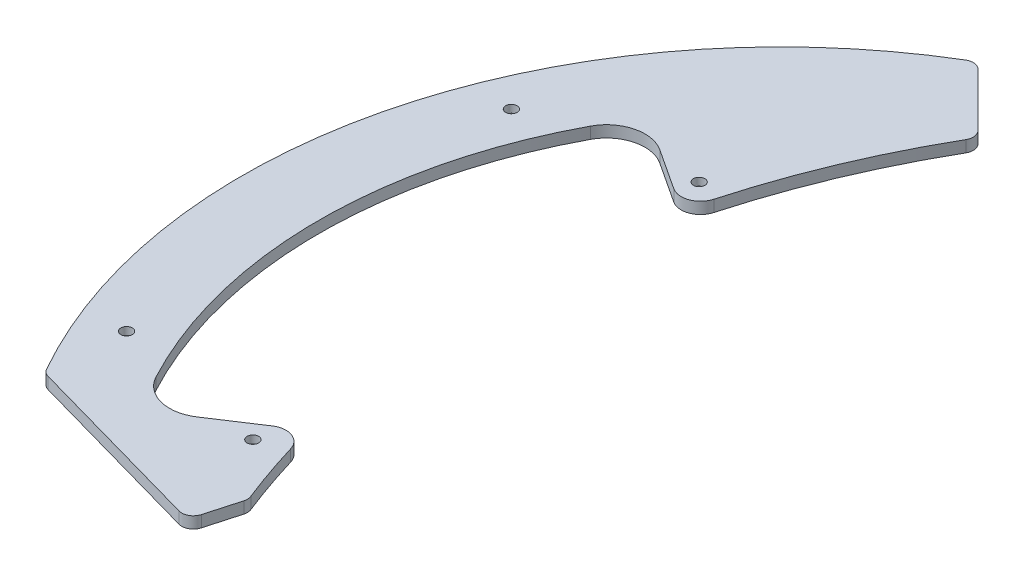
SolidWorks part; units mm, degrees
material "1060 Alloy"
ref_plane "Front Plane" through (0, 0, 0) normal (0, 0, 1) x (1, 0, 0)
ref_plane "Top Plane" through (0, 0, 0) normal (0, 1, 0) x (1, 0, 0)
ref_plane "Right Plane" through (0, 0, 0) normal (1, 0, 0) x (0, 0, -1)
sketch "Sketch1" plane through (0, 0, 0) normal (0, 1, 0) x (1, 0, 0)
  circle A0 centre (0, 0) radius 140
  dimension "D1" = 280
extrude "Boss-Extrude1" add sketch "Sketch1" along normal blind 3
sketch "Sketch17" plane through (0, 0, 0) normal (0, -1, 0) x (1, 0, 0)
  line L0 (-50, 90) -> (-121.2436, 70)
  line L1 (-50, 90) -> (50, 90)
  line L2 (-121.2436, 70) -> (-121.2436, 140)
  line L3 (-121.2436, 140) -> (121.2436, 140)
  line L4 (121.2436, 140) -> (121.2436, 70)
  line L5 (121.2436, 70) -> (50, 90)
  circle A0 centre (0, 0) radius 140 construction
  dimension "D1" = 90
  dimension "D2" = 50
  dimension "D3" = 50
  dimension "D4" = 70
extrude "Cut-Extrude1" cut sketch "Sketch17" against normal up to next
sketch "Sketch19" plane through (0, 3, 0) normal (0, 1, 0) x (1, 0, 0)
  line L0 (-68.5894, 68.5894) -> (68.5894, -68.5894) construction
  line L1 (97, 40.1787) -> (40.1787, 97) construction
  line L2 (40.1787, 97) -> (-40.1787, 97) construction
  line L3 (-40.1787, 97) -> (-97, 40.1787) construction
  line L4 (-97, 40.1787) -> (-97, -40.1787) construction
  line L5 (-97, -40.1787) -> (-40.1787, -97) construction
  line L6 (-40.1787, -97) -> (40.1787, -97) construction
  line L7 (40.1787, -97) -> (97, -40.1787) construction
  line L8 (97, -40.1787) -> (97, 40.1787) construction
  line L9 (68.5894, 68.5894) -> (-68.5894, -68.5894) construction
  circle A0 centre (-79.196, -57.9828) radius 1.5
  circle A1 centre (-79.196, 57.9828) radius 1.5
  circle A2 centre (79.196, 57.9828) radius 1.5
  circle A3 centre (79.196, -57.9828) radius 1.5
  circle A4 centre (0, 0) radius 97 construction
  circle A5 centre (-57.9828, 79.196) radius 1.5
  circle A6 centre (57.9828, 79.196) radius 1.5
  circle A7 centre (57.9828, -79.196) radius 1.5
  circle A8 centre (-57.9828, -79.196) radius 1.5
  dimension "D5" = 3
  dimension "D1" = 15
  dimension "D6" = 97
extrude "Cut-Extrude3" cut sketch "Sketch19" against normal up to next
sketch "Sketch20" plane through (0, 3, 0) normal (0, 1, 0) x (1, 0, 0)
  line L0 (-70, 121.2436) -> (-50, 101.2436)
  line L1 (-50, 101.2436) -> (50, 101.2436)
  line L2 (50, 101.2436) -> (70, 121.2436)
  arc A1 (121.2436, -70) -> (-121.2436, -70) centre (0, 0) ccw construction
  dimension "D1" = 140
  dimension "D2" = 100
  dimension "D3" = 50
extrude "Cut-Extrude4" cut sketch "Sketch20" against normal up to next
sketch "Sketch21" plane through (0, 3, 0) normal (0, 1, 0) x (1, 0, 0)
  line L0 (-52.1633, 87.3282) -> (0, 50)
  line L1 (0, 50) -> (52.1633, 87.3282)
  line L2 (66.2648, 73.5916) -> (30, 20)
  line L3 (30, 20) -> (67.2983, -75.56)
  line L4 (49.6537, -84.7301) -> (0, -10) construction
  line L5 (0, -10) -> (-49.6537, -84.7301) construction
  line L6 (-67.2983, -75.56) -> (-30, 20)
  line L7 (-30, 20) -> (-66.2648, 73.5916)
  line L8 (-67.2983, -75.56) -> (-72.9344, -90)
  line L9 (-72.9344, -90) -> (72.9344, -90)
  line L10 (72.9344, -90) -> (67.2983, -75.56)
  line L11 (-50, -90) -> (50, -90) construction
  line L12 (-68.5894, 68.5894) -> (68.5894, -68.5894) construction
  line L13 (97, 40.1787) -> (40.1787, 97) construction
  line L14 (40.1787, 97) -> (-40.1787, 97) construction
  line L15 (-40.1787, 97) -> (-97, 40.1787) construction
  line L16 (-97, 40.1787) -> (-97, -40.1787) construction
  line L17 (-97, -40.1787) -> (-40.1787, -97) construction
  line L18 (-40.1787, -97) -> (40.1787, -97) construction
  line L19 (40.1787, -97) -> (97, -40.1787) construction
  line L20 (97, -40.1787) -> (97, 40.1787) construction
  line L21 (68.5894, 68.5894) -> (-68.5894, -68.5894) construction
  arc A0 (-66.2648, 73.5916) -> (-52.1633, 87.3282) centre (-57.9828, 79.196) cw
  arc A1 (66.2648, 73.5916) -> (52.1633, 87.3282) centre (57.9828, 79.196) ccw
  arc A2 (-49.6537, -84.7301) -> (-67.2983, -75.56) centre (-57.9828, -79.196) cw construction
  arc A3 (67.2983, -75.56) -> (49.6537, -84.7301) centre (57.9828, -79.196) cw construction
  circle A5 centre (0, 0) radius 97 construction
  dimension "D2" = 10
  dimension "D3" = 15
  dimension "D8" = 97
extrude "Cut-Extrude5" [suppressed] cut sketch "Sketch21" against normal up to next
fillet "Fillet1" [suppressed] radius 20
fillet "Fillet2" radius 10 2 edges at (50, 1.5, -101.2436) (-50, 1.5, -101.2436)
sketch "Sketch22" plane through (0, 3, 0) normal (0, 1, 0) x (1, 0, 0)
  line L1 (85, 24) -> (118, 24)
  line L2 (85, 24) -> (85, -24)
  line L3 (85, -24) -> (118, -24)
  line L4 (118, 24) -> (118, -24)
  line L5 (-118, 26) -> (-85, 26)
  line L6 (-118, 26) -> (-118, -27)
  line L7 (-118, -27) -> (-85, -27)
  line L8 (-85, 26) -> (-85, -27)
  dimension "D1" = 85
  dimension "D2" = 85
  dimension "D3" = 48
  dimension "D4" = 53
  dimension "D5" = 33
  dimension "D6" = 33
  dimension "D7" = 26
  dimension "D8" = 24
extrude "Cut-Extrude6" [suppressed] cut sketch "Sketch22" against normal up to next
fillet "Fillet3" [suppressed] radius 3
sketch "Sketch23" plane through (0, 3, 0) normal (0, 1, 0) x (1, 0, 0)
  line L0 (-66.3365, -71.9548) -> (-73.1897, -96.3671)
  line L1 (-70, 121.2436) -> (-52.9289, 104.1725) construction
  line L2 (-121.2436, -70) -> (-50, -90) construction
  arc A0 (-52.9289, 104.1725) -> (-66.3365, -71.9548) centre (119.2928, 2.4883) ccw
  arc A3 (-66.3365, -71.9548) -> (-52.9289, -99.196) centre (119.2928, 2.4883) ccw construction
  circle A4 centre (-57.9828, -79.196) radius 1.5 construction
  dimension "D2" = 20
  dimension "D3" = 200
  dimension "D4" = 90
  dimension "D5" = 10
extrude "Cut-Extrude8" cut sketch "Sketch23" against normal through all and the other way through all
sketch "Sketch24" plane through (0, 3, 0) normal (0, 1, 0) x (1, 0, 0)
  line L0 (0, 0) -> (-100.309, 65.8643)
  line L1 (-100.309, -65.8643) -> (0, 0)
  arc A0 (-100.309, 65.8643) -> (-100.309, -65.8643) centre (0, 0) ccw
  circle A1 centre (-79.196, 57.9828) radius 1.5 construction
  circle A2 centre (-79.196, -57.9828) radius 1.5 construction
  arc A3 (-70, 121.2436) -> (-121.2436, -70) centre (0, 0) ccw construction
  dimension "D2" = 5
  dimension "D3" = 20
  dimension "D1" = 5
extrude "Cut-Extrude9" cut sketch "Sketch24" against normal up to next
fillet "Fillet4" radius 5 2 edges at (-74.0638, 1.5, 48.6314) (-75.1422, 1.5, -49.3395)
fillet "Fillet6" radius 10 2 edges at (-100.309, 1.5, -65.8643) (-100.309, 1.5, 65.8643)
sketch "Sketch25" plane through (0, 3, 0) normal (0, 1, 0) x (1, 0, 0)
  circle A0 centre (-120, 50) radius 1.5
  circle A1 centre (-120, -50) radius 1.5
  dimension "D1" = 3
  dimension "D2" = 50
  dimension "D3" = 50
  dimension "D4" = 120
extrude "Cut-Extrude10" cut sketch "Sketch25" against normal up to next
fillet "Fillet5" radius 3 5 edges at (-70, 1.5, -121.2436) (-66.3365, 1.5, 71.9548) (-69.8389, 1.5, 84.4307) (-121.2436, 1.5, 70) (-52.9289, 1.5, -104.1725)
sketch "Sketch26" plane through (0, 0, 0) normal (0, -1, 0) x (1, 0, 0)
  circle A0 centre (-79.196, 57.9828) radius 3
  circle A1 centre (-120, 50) radius 3
  circle A2 centre (-120, -50) radius 3
  circle A3 centre (-79.196, -57.9828) radius 3
  dimension "D1" = 6
extrude "Cut-Extrude11" cut sketch "Sketch26" against normal blind 1
equation "\"D3@Sketch20\" = \"D2@Sketch20\" / 2"
